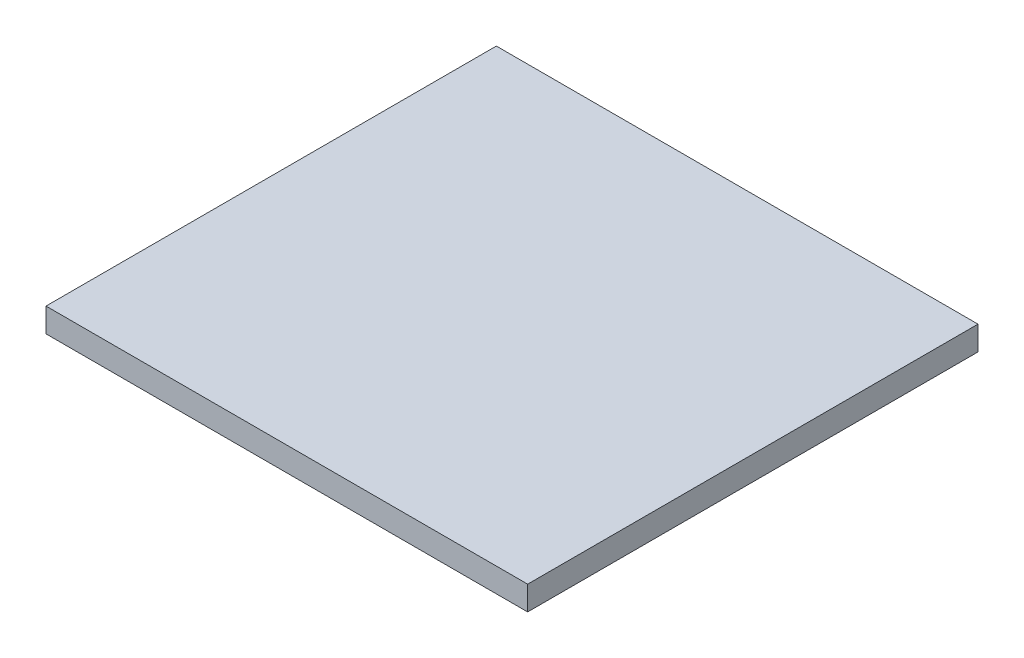
SolidWorks part; units mm, degrees
ref_plane "Front Plane" through (0, 0, 0) normal (0, 0, 1) x (1, 0, 0)
ref_plane "Top Plane" through (0, 0, 0) normal (0, 1, 0) x (1, 0, 0)
ref_plane "Right Plane" through (0, 0, 0) normal (1, 0, 0) x (0, 0, -1)
sketch "Sketch1" plane through (0, 0, 0) normal (0, 1, 0) x (1, 0, 0)
  line L1 (100, -93.5) -> (-100, -93.5)
  line L2 (100, -93.5) -> (100, 93.5)
  line L3 (100, 93.5) -> (-100, 93.5)
  line L4 (-100, -93.5) -> (-100, 93.5)
  line L5 (100, -93.5) -> (-100, 93.5) construction
  line L6 (100, 93.5) -> (-100, -93.5) construction
  point P0 (0, 0)
  dimension "D1" = 187
  dimension "D2" = 200
extrude "Boss-Extrude1" add sketch "Sketch1" along normal blind 10
